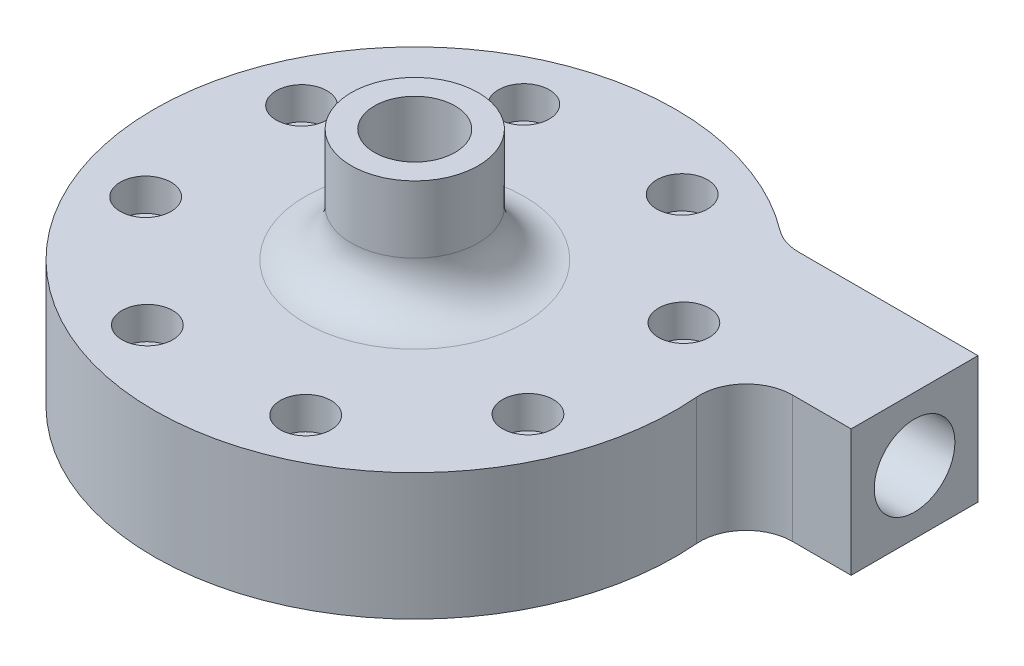
SolidWorks part; units mm, degrees
material "1060 Alloy"
ref_plane "Front" through (0, 0, 0) normal (0, 0, 1) x (1, 0, 0)
ref_plane "Top" through (0, 0, 0) normal (0, 1, 0) x (1, 0, 0)
ref_plane "Right" through (0, 0, 0) normal (1, 0, 0) x (0, 0, -1)
sketch "Sketch1" plane through (0, 0, 0) normal (0, 1, 0) x (1, 0, 0)
  line L0 (0, 0) -> (2.6693, 30.5101) construction
  line L1 (2.6693, 30.5101) -> (60.9409, 35.6082) construction
  line L2 (9.0461, 29.2602) -> (60.9409, 29.2602) construction
  line L3 (14.512, 26.9702) -> (60.9409, 22.9082) construction
  line L4 (0, 0) -> (56.2352, -4.9199) construction
  line L5 (14.512, 31.5462) -> (14.512, 29.2602) construction
  line L6 (14.512, 29.2602) -> (14.512, 26.9702) construction
  line L7 (60.9409, 29.2602) -> (60.9409, 35.6082) construction
  line L8 (60.9409, 29.2602) -> (60.9409, 22.9082) construction
  line L9 (78.9409, 29.2602) -> (78.9409, 42.9915)
  line L10 (78.9409, 37.9915) -> (60.9409, 37.9915) construction
  line L11 (78.9409, 37.9915) -> (78.9409, 20.529) construction
  line L12 (78.9409, 20.529) -> (60.9409, 20.529) construction
  line L13 (60.9409, 37.9915) -> (60.9409, 20.529) construction
  line L14 (78.9409, 42.9915) -> (40.0937, 42.9915)
  line L15 (78.9409, 29.2602) -> (78.9409, 15.529)
  line L16 (78.9409, 15.529) -> (66.2196, 15.529)
  arc A0 (34.06, 45.0169) -> (56.2543, 4.6969) centre (0, 0) ccw
  circle A1 centre (0, 0) radius 30.6267 construction
  arc A2 (66.2196, 15.529) -> (56.2543, 4.6969) centre (66.2196, 5.529) ccw
  arc A3 (40.0937, 42.9915) -> (34.06, 45.0169) centre (40.0937, 52.9915) cw
  dimension "D1" = 112.9
  dimension "D2" = 61.2534
  dimension "D13" = 10
  dimension "D4" = 2.286
  dimension "D3" = 2.29
  dimension "D5" = 5
  dimension "D6" = 5
  dimension "D7" = 5
  dimension "D8" = 12.7
  dimension "D9" = 17.4625
  dimension "D10" = 18
  dimension "D11" = 5
  dimension "D12" = 5
extrude "main body" add sketch "Sketch1" along normal blind 27.4625
ref_plane "body midsection" through (0, 13.7313, 0) normal (0, 1, 0) x (1, 0, 0)
sketch "Sketch2" plane through (0, 0, 0) normal (0, 0, 1) x (1, 0, 0)
  line L0 (0, 27.4625) -> (0, 0) construction
  line L1 (56.45, 27.4625) -> (-56.45, 27.4625) construction
  line L2 (0, 27.4625) -> (5.4102, 27.4625)
  line L3 (0, 13.102) -> (30.6267, 13.102) construction
  line L4 (30.6267, 16.0173) -> (5.4102, 27.7759)
  line L5 (5.4102, 27.4625) -> (5.4102, 27.7759)
  line L6 (30.6267, 16.0173) -> (0, 16.0172) construction
  line L8 (58.025, 13.7313) -> (-58.025, 13.7313) construction
  line L9 (-56.45, 13.7313) -> (0, 13.7313) construction
  line L10 (-56.45, 0) -> (56.45, 0) construction
  line L11 (30.6267, 0) -> (0, 0)
  line L12 (0, 0) -> (0, 27.4625)
  line L13 (26.6319, 13.7313) -> (56.45, 13.7313) construction
  line L14 (0, 13.7313) -> (26.6319, 13.7313) construction
  line L15 (26.6319, 13.7313) -> (26.6319, 17.88) construction
  line L16 (26.6319, 17.88) -> (0, 17.88) construction
  line L17 (-56.45, 27.4625) -> (-56.45, 0) construction
  line L18 (30.6267, 16.0173) -> (30.6267, 0)
  line L19 (56.45, 0) -> (56.45, 27.4625) construction
  dimension "D4" = 2.286
  dimension "D1" = 30.6267
  dimension "D3" = 26.6319
  dimension "D5" = 5.4102
  dimension "D2" = 4.778
  dimension "D6" = 14.6738
revolve "main chamber" cut sketch "Sketch2" angle 360 about L12
sketch "Sketch4" plane through (0, 0, 0) normal (0, 0, 1) x (1, 0, 0)
  line L0 (5.4102, 27.4625) -> (5.4102, 36.9475)
  line L2 (5.4102, 36.9475) -> (8.7313, 36.9475)
  line L3 (8.7313, 36.9475) -> (8.7313, 51.9475)
  line L4 (8.7313, 51.9475) -> (13.7313, 51.9475)
  line L5 (13.7313, 51.9475) -> (13.7313, 37.4625)
  line L7 (0, 0) -> (0, 49.2593) construction
  line L8 (56.45, 0) -> (-56.45, 0) construction
  line L9 (5.4102, 26.9475) -> (-5.4102, 26.9475) construction
  line L10 (5.4102, 27.4625) -> (23.7313, 27.4625)
  arc A0 (13.7313, 37.4625) -> (23.7313, 27.4625) centre (23.7313, 37.4625) ccw
  dimension "D5" = 10
  dimension "D1" = 10
  dimension "D2" = 8.7313
  dimension "D3" = 5
  dimension "D4" = 15
revolve "inlet" add sketch "Sketch4" angle 360 about L7
sketch "Sketch3" plane through (0, 13.7313, 0) normal (0, 1, 0) x (1, 0, 0)
  line L0 (2.6693, 30.5101) -> (60.9409, 35.6082)
  line L2 (60.9409, 29.2602) -> (2.5599, 29.2602)
  line L3 (0, 0) -> (2.6693, 30.5101) construction
  line L4 (2.5599, 29.2602) -> (2.6693, 30.5101)
  line L5 (60.9409, 35.6082) -> (60.9409, 37.9915)
  line L6 (60.9409, 37.9915) -> (78.9409, 37.9915)
  line L7 (78.9409, 37.9915) -> (78.9409, 29.2602)
  line L8 (78.9409, 29.2602) -> (60.9409, 29.2602)
revolve "expansion cone and outlet" cut sketch "Sketch3" angle 360 about L2
sketch "Sketch5" plane through (0, 27.4625, 0) normal (0, 1, 0) x (1, 0, 0)
  line L1 (16.6948, 41.1957) -> (40.9348, 17.3248) construction
  line L3 (9.0461, 29.2602) -> (60.9409, 29.2602) construction
  circle A0 centre (0, 0) radius 44.45 construction
  circle A1 centre (40.9348, 17.3248) radius 2.9766
  circle A2 centre (0, 0) radius 44.45 construction
  circle A3 centre (41.1957, -16.6948) radius 2.9766
  circle A4 centre (0, 0) radius 44.45 construction
  circle A5 centre (17.3248, -40.9348) radius 2.9766
  circle A6 centre (0, 0) radius 44.45 construction
  circle A7 centre (-16.6948, -41.1957) radius 2.9766
  circle A8 centre (0, 0) radius 44.45 construction
  circle A9 centre (-40.9348, -17.3248) radius 2.9766
  circle A10 centre (0, 0) radius 44.45 construction
  circle A11 centre (-41.1957, 16.6948) radius 2.9766
  circle A12 centre (0, 0) radius 44.45 construction
  circle A13 centre (-17.3248, 40.9348) radius 2.9766
  circle A14 centre (0, 0) radius 44.45 construction
  circle A15 centre (16.6948, 41.1957) radius 2.9766
  point P5 (28.8148, 29.2602)
  point P30 (0, 0)
  dimension "D1" = 88.9
  dimension "D2" = 5.9531
  dimension "D4" = 8
sketch "Sketch6" plane through (0, 27.4625, 0) normal (0, 1, 0) x (1, 0, 0)
  circle A0 centre (40.9348, 17.3248) radius 5.5
  circle A1 centre (41.1957, -16.6948) radius 5.5
  circle A2 centre (17.3248, -40.9348) radius 5.5
  circle A3 centre (-16.6948, -41.1957) radius 5.5
  circle A4 centre (-40.9348, -17.3248) radius 5.5
  circle A5 centre (-41.1957, 16.6948) radius 5.5
  circle A6 centre (-17.3248, 40.9348) radius 5.5
  circle A7 centre (16.6948, 41.1957) radius 5.5
  point P19 (0, 0)
  dimension "D1" = 11
  dimension "D2" = 8
ref_plane "exit axial plane" through (0, 0, -29.2602) normal (0, 0, -1) x (-1, 0, 0)
extrude "bolt clearances" cut sketch "Sketch5" against normal through all
extrude "bolt head clearance" cut sketch "Sketch6" against normal blind 7
equation "\"bearing OD\" = 30mm"
equation "\"bearing ID\"= 10mm"
equation "\"bearing depth\"= 9mm"
equation "\"bearing outer race thickness\"= 1mm"
equation "\"bearing inner race thickness\"= 1mm"
equation "\"bearing bore\" = \"bearing depth\" + 1mm"
equation "\"z\" = 8 \t\t\t'number of blades"
equation "\"de\" = 0.426in\t\t\t'entrance eye diameter"
equation "\"d2\" = 2.097in \t\t\t'outer diameter of the impeller"
equation "\"d_exit\" = 0.18in \t\t'volute throat aka D4"
equation "\"theta\" = 25\t\t\t'angle of blades from inner to outer "
equation "\"b2\" = .07in\t\t\t\t\t\t\t'tip height from disc surface at d2"
equation "\"b1\" = \"b2\" + (\"d2\"/2 - \"de\"/2)*tan(\"theta\") \t\t\t'tip height from disc surface at inlet eye"
equation "\"s\"=\"ce\" - \"z\"*\"s_open\""
equation "\"impeller upper clearance\"= .5mm"
equation "\"impeller horizontal clearance\"= (\"d2\"*1.15 - \"d2\")/2 \t\t'clearance based on D2-D3 ratio for circular volute, ranges 1.15 to 1.2"
equation "\"impeller bottom clearance\"= .5mm"
equation "\"impeller base thickness\"= 2mm"
equation "\"impeller dowel diameter\" = 2mm"
equation "\"impeller bolt head diameter\" = \"m4 head bore diameter\""
equation "\"impeller bolt head depth\" = 4mm"
equation "\"impeller bolt stop depth\" = 3mm"
equation "\"impeller bolt bore\" = \"m4 clearance\""
equation "\"impeller shaft bore depth\" = 12mm"
equation "\"impeller shaft bore\" = 8mm"
equation "\"impeller boss depth\" = \"impeller shaft bore depth\"+\"impeller bolt stop depth\"+\"impeller bolt head depth\"-\"impeller base thickness\""
equation "\"impeller boss diameter\" = \"upper seal ID\""
equation "\"impeller dowel length\" = 2mm*2 + \"impeller shaft bore\""
equation "\"coupler motor shaft hole ID\"= 8mm"
equation "\"coupler OD\"= 17mm"
equation "\"coupler length\"= 25mm"
equation "\"motor OD\" = 64mm"
equation "\"motor shaft diameter\"= 8mm"
equation "\"motor shaft pride\"= 32mm"
equation "\"motor to bearing plate distance\" = \"motor shaft pride\" + 2mm +\"coupler length\"/2"
equation "\"square plate bolt bore\" = 8mm"
equation "\"square plate bolt head diameter\" = 13.5mm"
equation "\"square plate bolt head depth\" = 8mm"
equation "\"square plate bolt pattern diameter\"= 3.5in"
equation "\"motor mount center bore\"= \"coupler OD\"+ 4mm"
equation "\"motor mount post radius\"= ( 3 * \"square plate bolt bore\" ) / 2"
equation "\"motor mount m4 screw hole diameter\"= 4mm"
equation "\"motor mount m4 head diameter\"= 7.25mm"
equation "\"motor mount m4 head depth\"= 4mm"
equation "\"motor mount m4 pattern diamater\" = 30mm"
equation "\"motor mount plate thickness\"= 8mm + \"motor mount m4 head depth\""
equation "\"bearing plate stop ID\" = \"bearing OD\" - 4mm"
equation "\"bearing plate stop depth\" = 3mm"
equation "\"bearing plate thickness\" = \"bearing bore\" + \"bearing plate stop depth\" + \"shaft bearing stop length\""
equation "\"shaft coupler section diameter\" = 8mm"
equation "\"shaft coupler section length\" = \"motor to bearing plate distance\" - \"motor shaft pride\" - 2mm"
equation "\"shaft bearing section diameter\" = \"bearing ID\""
equation "\"shaft bearing section length\" = \"bearing plate stop depth\" + \"bearing depth\""
equation "\"shaft bearing stop diameter\" = \"bearing ID\" + 4mm"
equation "\"shaft bearing stop length\" = 3mm"
equation "\"impeller cavity center height\"= \"impeller bottom clearance\" + \"impeller upper clearance\" + \"impeller center height\""
equation "\"impeller cavity diameter\"= 2 * \"impeller horizontal clearance\" + \"d2\" \t\t\t\t\t\t\t\t\t'called D3 analytically"
equation "\"impeller cavity outer height\"= \"impeller bottom clearance\" + \"impeller upper clearance\" + \"impeller base thickness\" + \"b2\" \t\t'this is height at impeller diameter d2, not at d3"
equation "\"impeller housing thickness\"= \"impeller housing exit threaded diameter\" + 2*\"impeller housing outlet grip\""
equation "\"impeller housing diameter\" = \"square plate bolt pattern diameter\" + 2*\"motor mount post radius\""
equation "\"impeller housing bolt count\" = 8"
equation "\"impeller housing bolt diameter\" = \"m6 clearance\""
equation "\"impeller housing bolt pattern diameter\" = 3.5in"
equation "\"impeller housing threaded inlet diameter\" = 0.6875in \t\t'this is the 11/16 drill size for 1/2 npt fitting"
equation "\"impeller housing threaded inlet depth\"= 15mm"
equation "\"impeller housing exit threaded diameter\"= 0.6875in \t\t'this is the 11/16 drill size for 1/2 npt fitting"
equation "\"impeller housing exit threaded depth\"= 18mm"
equation "\"impeller housing diffuser conical angle\"=10"
equation "\"impeller housing diffuser tangent angle\"=5"
equation "\"impeller housing diffuser final diameter\" = .5in"
equation "\"impeller housing outlet grip\" = 5mm"
equation "\"D1@Sketch1\"=\"impeller housing diameter\""
equation "\"D2@Sketch1\"=\"impeller cavity diameter\""
equation "\"D4@Sketch1\"=\"d_exit\"/2"
equation "\"D5@Sketch1\"=\"impeller housing diffuser tangent angle\""
equation "\"D6@Sketch1\"=\"impeller housing diffuser conical angle\"/2"
equation "\"D7@Sketch1\"=\"impeller housing diffuser conical angle\"/2"
equation "\"D8@Sketch1\"=\"impeller housing diffuser final diameter\""
equation "\"D9@Sketch1\"=\"impeller housing exit threaded diameter\""
equation "\"D10@Sketch1\"=\"impeller housing exit threaded depth\""
equation "\"D11@Sketch1\"=\"impeller housing outlet grip\""
equation "\"D12@Sketch1\"=\"impeller housing outlet grip\""
equation "\"D1@main body\" = \"impeller housing thickness\""
equation "\"D1@Sketch2\"=\"impeller cavity diameter\"/2"
equation "\"D3@Sketch2\"= \"d2\" / 2"
equation "\"D2@Sketch2\"=\"impeller cavity outer height\""
equation "\"D5@Sketch2\"=\"de\"/2"
equation "\"D6@Sketch2\" = \"impeller center height\" + \"impeller bottom clearance\" + \"impeller upper clearance\""
equation "\"de_length\" = 10mm\t\t'entrance eye consistent length"
equation "\"D2@Sketch4\"=\"impeller housing threaded inlet diameter\"/2"
equation "\"D3@Sketch4\"=\"impeller housing outlet grip\""
equation "\"D4@Sketch4\"=\"impeller housing threaded inlet depth\""
equation "\"D1@Sketch5\"=\"impeller housing bolt pattern diameter\""
equation "\"D2@Sketch5\"=\"m6 clearance\""
equation "\"end mill size\" = 0.375in\t'for 3/8 endmill"
equation "\"ae\" = 3.14*(\"de\"^2)/4\t\t'entrance eye area'"
equation "\"ce\" = 3.14*\"de\"\t\t'entrance eye circumference"
equation "\"av_ratio\" = .325\t\t'ratio of av/ae at N_s of 470, range is .275 to .375, .325 ideal. High ratio means bigger area means smaller blades"
equation "\"av\" = \"ae\"*\"av_ratio\"\t\t'area between just two blades"
equation "\"s_open\" = \"av\"/\"b1\"\t\t'width of open area"
equation "\"impeller center height\" = \"impeller base thickness\" + \"b1\"\t'impeller height at de"
equation "\"impeller outer height\" = \"impeller base thickness\" + \"b2\"\t'impeller height at de"
equation "\"shaft impeller section diameter\" = \"impeller shaft bore\""
equation "\"shaft impeller section length\" = \"upper seal plate thickness\" + \"upper seal plate riser\" + \"impeller bottom clearance\" + \"impeller base thickness\" - \"impeller bolt head depth\" - \"impeller bolt stop depth\""
equation "\"m6 clearance\" = 0.234375in\t'this is 15/64 bit = 5.95mm, could use 6mm bit, B bit for 6.04mm or 1/4 bit for 6.35mm"
equation "\"m6 tap\" = 5mm\t\t\t'5mm is appropriate, could use 13/64 or #5,6,7"
equation "\"m6 head bore diameter\" = 11mm\t\t"
equation "\"m6 head bore depth\" = 7mm\t'actual is 6mm"
equation "\"m8 clearance\" = 0.3125in\t'this is 5/16in for 7.93mm, could use 8mm, O,P, or 21/64"
equation "\"m8 tap\" = 0.265625in\t\t'this is 17/64 for 6.746875mm"
equation "\"m8 head bore diameter\" = 14mm"
equation "\"m8 head bore depth\" = 9mm\t'actual is 8mm"
equation "\"D1@Sketch6\"=\"m6 head bore diameter\""
equation "\"D1@bolt head clearance\" = \"m6 head bore depth\""
equation "\"lower seal OD\" = .917in\t\t'this is https://www.mcmaster.com/#9281k121/=174001b"
equation "\"lower seal ID\"= .375in"
equation "\"lower seal depth\" = .625in + .218in"
equation "\"lower seal bore\" = \"lower seal depth\" + 1mm"
equation "\"upper seal OD\" = 1.125in\t'this is https://www.mcmaster.com/#5154t33/=173zuau, needs to be visually inspected before machining!"
equation "\"upper seal ID\"= 0.625in"
equation "\"upper seal depth\"= .25in\t'aka height; these values need to be confirmed by inspection!! We may want to compress the height."
equation "\"upper seal bore\" = \"upper seal depth\" + 1mm"
equation "\"big o-ring thickness\" = .139in"
equation "\"big o-ring OD\" = 2.734in"
equation "\"big o-ring ID\" = 3.012in"
equation "\"big o-ring groove depth\" = \"big o-ring thickness\"*4/5"
equation "\"lower seal plate lip depth\" = 2mm"
equation "\"lower seal plate lip ID\" = \"lower seal OD\" - 3mm"
equation "\"lower seal plate thickness\" = \"lower seal plate lip depth\" + \"lower seal bore\""
equation "\"shaft lower seal section diameter\" = \"lower seal ID\""
equation "\"shaft lower seal section length\" = \"lower seal plate thickness\" + 1mm"
equation "\"upper seal plate thickness\" = \"upper seal plate pressure hole diameter\"*3"
equation "\"upper seal plate lip ID\" = \"upper seal OD\" - 3mm"
equation "\"upper seal plate riser\" = \"impeller housing thickness\"/2 - \"b2\"/2 - \"impeller base thickness\" - \t\"impeller bottom clearance\"\t\t\t'this offsets the gap under the housing"
equation "\"upper seal plate pressure hole diameter\" = .125in\t'this is 1/8 drill "
equation "\"upper seal plate pressure tap diameter\" = .328125in \t'this is 21/64 drill for a 1/8 ANPT tap"
equation "\"upper seal plate pressure tap grip\" = 4mm\t\t'this is the area around the tap so it doesn't crack"
equation "\"upper seal plate pressure tap depth\" = 12"
equation "\"m4 clearance\" = 0.171875in \t'this is 11/64 bit for 4.36mm"
equation "\"m4 tap\" = 0.125in\t\t'this is 1/8 bit for 3.17mm"
equation "\"m4 head bore diameter\" = 7.5mm"
equation "\"m4 head bore depth\" = 5mm\t'actual is ~4mm"
equation "\"D4@Sketch2\"=\"d_exit\"/2"
